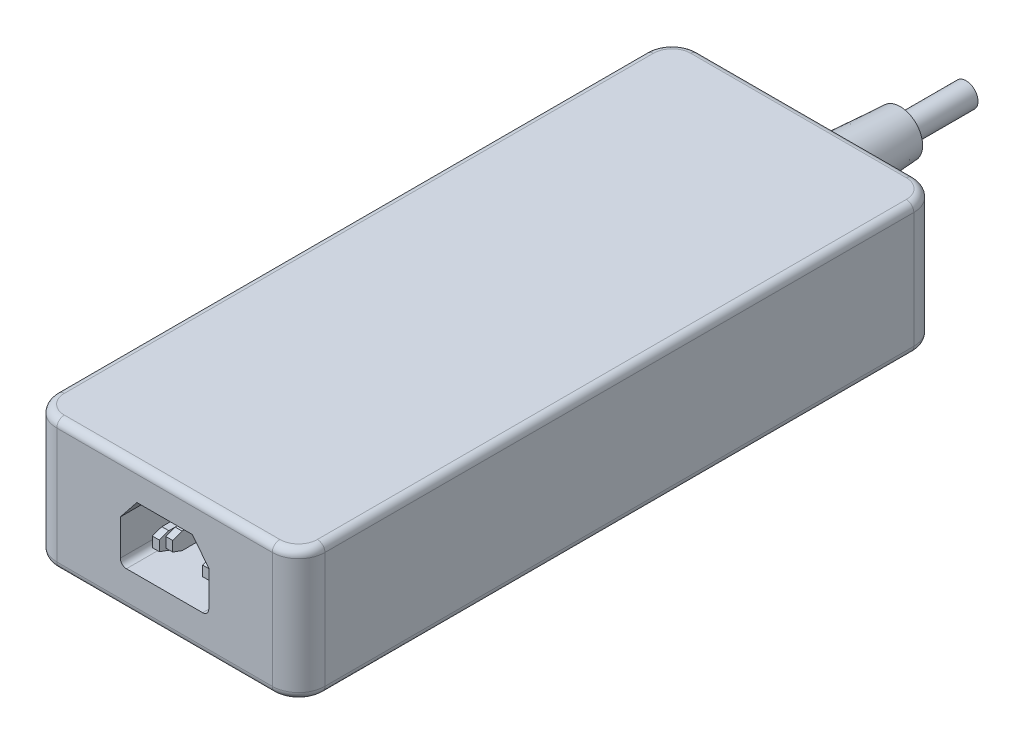
SolidWorks part; units mm, degrees
ref_plane "Front Plane" through (0, 0, 0) normal (0, 0, 1) x (1, 0, 0)
ref_plane "Top Plane" through (0, 0, 0) normal (0, 1, 0) x (1, 0, 0)
ref_plane "Right Plane" through (0, 0, 0) normal (1, 0, 0) x (0, 0, -1)
sketch "Sketch1" plane through (0, 0, 0) normal (0, 0, 1) x (1, 0, 0)
  line L0 (36.195, 17.6784) -> (-36.195, -17.6784) construction
  line L1 (-36.195, 17.6784) -> (36.195, 17.6784)
  line L2 (-36.195, 17.6784) -> (-36.195, -17.6784)
  line L3 (-36.195, -17.6784) -> (36.195, -17.6784)
  line L4 (36.195, 17.6784) -> (36.195, -17.6784)
  dimension "D1" = 35.3568
  dimension "D2" = 72.39
extrude "Boss-Extrude1" add sketch "Sketch1" along normal mid plane 173.228
fillet "Fillet1" radius 7.112 4 edges at (36.195, 0, -86.614) (-36.195, 0, -86.614) (36.195, 0, 86.614) (-36.195, 0, 86.614)
fillet "Fillet2" radius 2.032 16 edges at (-34.1119, -17.6784, -84.5309) (-36.195, -17.6784, 0) (-34.1119, -17.6784, 84.5309) (0, -17.6784, 86.614) (34.1119, -17.6784, 84.5309) (36.195, -17.6784, 0) (34.1119, -17.6784, -84.5309) (0, -17.6784, -86.614) (34.1119, 17.6784, 84.5309) (0, 17.6784, 86.614) (-34.1119, 17.6784, 84.5309) (-36.195, 17.6784, 0) (-34.1119, 17.6784, -84.5309) (0, 17.6784, -86.614) (34.1119, 17.6784, -84.5309) (36.195, 17.6784, 0)
sketch "Sketch2" plane through (0, 0, 86.614) normal (0, 0, 1) x (1, 0, 0)
  line L0 (0, 0) -> (0, 15.6464) construction
  line L1 (29.083, 15.6464) -> (-29.083, 15.6464) construction
  line L2 (0, 0) -> (-29.083, 0) construction
  line L3 (-29.083, 15.6464) -> (-29.083, -15.6464) construction
  line L4 (7.474, 9.0551) -> (-7.474, 9.0551)
  line L5 (-7.474, 9.0551) -> (-11.938, 3.4544)
  line L6 (-11.938, 3.4544) -> (-11.938, -7.8359)
  line L7 (-11.938, -7.8359) -> (11.938, -7.8359)
  line L8 (11.938, 3.4544) -> (11.938, -7.8359)
  line L9 (7.474, 9.0551) -> (11.938, 3.4544)
  line L10 (29.083, -17.6784) -> (-29.083, -17.6784) construction
  point P5 (0, -7.8359)
  point P16 (0, 9.0551)
  dimension "D1" = 16.891
  dimension "D2" = 23.876
  dimension "D3" = 9.8425
  dimension "D4" = 14.9479
  dimension "D5" = 11.2903
extrude "Cut-Extrude1" cut sketch "Sketch2" against normal blind 17.0561
fillet "Fillet3" radius 1.651 2 edges at (11.938, -7.8359, 78.0859) (-11.938, -7.8359, 78.0859)
sketch "Sketch3" plane through (0, 0, 69.5579) normal (0, 0, 1) x (1, 0, 0)
  line L0 (0, 0) -> (0, -7.8359) construction
  line L1 (-7.7216, -0.2159) -> (-5.842, -0.2159)
  line L2 (-7.7216, -0.2159) -> (-7.7216, -4.7879)
  line L3 (-7.7216, -4.7879) -> (-5.842, -4.7879)
  line L4 (-5.842, -0.2159) -> (-5.842, -4.7879)
  line L5 (-0.9398, 4.6736) -> (0.9398, 4.6736)
  line L6 (-0.9398, 4.6736) -> (-0.9398, 0.1016)
  line L7 (-0.9398, 0.1016) -> (0.9398, 0.1016)
  line L8 (0.9398, 4.6736) -> (0.9398, 0.1016)
  line L9 (-10.287, -7.8359) -> (10.287, -7.8359) construction
  line L10 (5.842, -0.2159) -> (5.842, -4.7879)
  line L11 (7.7216, -4.7879) -> (5.842, -4.7879)
  line L12 (7.7216, -0.2159) -> (7.7216, -4.7879)
  line L13 (7.7216, -0.2159) -> (5.842, -0.2159)
  line L14 (-10.287, -7.8359) -> (10.287, -7.8359) construction
  line L15 (0, 0) -> (0, 0.1016) construction
  dimension "D1" = 1.8796
  dimension "D2" = 4.572
  dimension "D3" = 3.048
  dimension "D4" = 11.684
  dimension "D5" = 7.9375
extrude "Boss-Extrude2" add sketch "Sketch3" along normal offset from surface (15.7861 mm away) 1.27 up to face at (0, -0.4633, 86.614)
sketch "Sketch4" plane through (0, 0, 85.344) normal (0, 0, 1) x (1, 0, 0)
  line L0 (7.7216, -4.7879) -> (7.7216, -0.2159) construction
  line L1 (-7.7216, -4.7879) -> (7.7216, -4.7879)
  line L2 (-7.7216, -4.7879) -> (-7.7216, -0.2159)
  line L3 (-7.7216, -0.2159) -> (7.7216, -0.2159)
  line L4 (7.7216, -4.7879) -> (7.7216, -0.2159)
  point P7 (7.7216, -0.2159)
extrude "Cut-Extrude2" cut sketch "Sketch4" against normal blind 3.175
chamfer "Chamfer1" distance 2.54 angle 20 6 edges at (0, 4.6736, 85.344) (0, 0.1016, 85.344) (-6.7818, -4.7879, 82.169) (6.7818, -4.7879, 82.169) (6.7818, -0.2159, 82.169) (-6.7818, -0.2159, 82.169) first distance on face at (0, 4.6736, 77.451) first distance on face at (0, 0.1016, 77.451) first distance on face at (-6.7818, -4.7879, 75.8635) first distance on face at (6.7818, -4.7879, 75.8635) first distance on face at (6.7818, -0.2159, 75.8635) first distance on face at (-6.7818, -0.2159, 75.8635)
sketch "Sketch5" plane through (0, 0, -86.614) normal (0, 0, -1) x (-1, 0, 0)
  circle A0 centre (0, 0) radius 7.62
  dimension "D1" = 15.24
extrude "Boss-Extrude3" add sketch "Sketch5" along normal blind 25.4 draft 3.5
sketch "Sketch7" plane through (0, 0, -112.014) normal (0, 0, -1) x (-1, 0, 0)
  circle A0 centre (0, 0) radius 3.2385
  dimension "D1" = 6.477
extrude "Boss-Extrude4" add sketch "Sketch7" along normal blind 32.766
sketch "Sketch8" plane through (0, 0, -144.78) normal (0, 0, -1) x (-1, 0, 0)
  circle A0 centre (0, 0) radius 10.8966
  dimension "D1" = 21.7932
extrude "Boss-Extrude5" add sketch "Sketch8" along normal blind 34.417
fillet "Fillet4" radius 0.635 2 edges at (-10.8966, 0, -144.78) (-10.8966, 0, -179.197)
sketch "Sketch9" plane through (0, 0, -179.197) normal (0, 0, -1) x (-1, 0, 0)
  circle A0 centre (0, 0) radius 3.2385 construction
  circle A1 centre (0, 0) radius 3.2385
extrude "Boss-Extrude6" add sketch "Sketch9" along normal blind 34.417
sketch "Sketch10" plane through (0, 0, -213.614) normal (0, 0, -1) x (-1, 0, 0)
  circle A0 centre (0, 0) radius 27.9004
extrude "Cut-Extrude3" cut sketch "Sketch10" against normal blind 83.82
